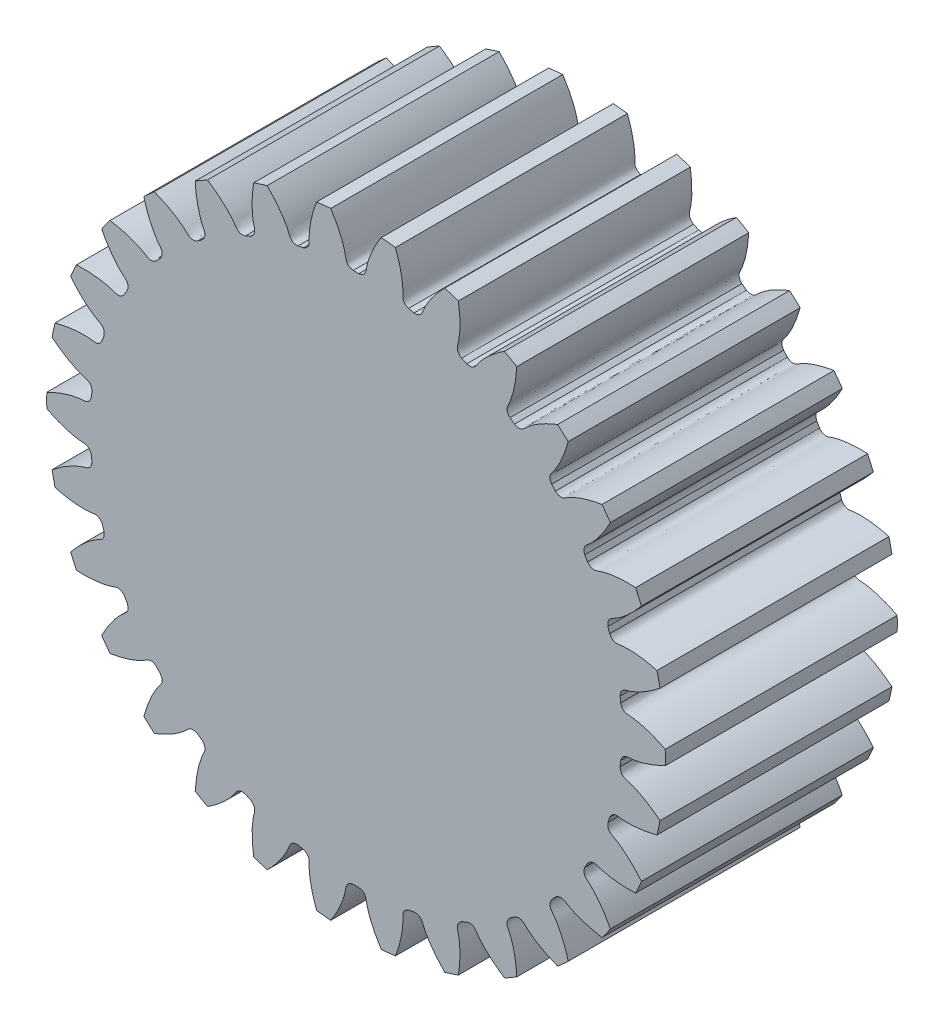
SolidWorks part; units mm, degrees
ref_plane "前视基准面" through (0, 0, 0) normal (0, 0, 1) x (1, 0, 0)
ref_plane "上视基准面" through (0, 0, 0) normal (0, 1, 0) x (1, 0, 0)
ref_plane "右视基准面" through (0, 0, 0) normal (1, 0, 0) x (0, 0, -1)
sketch "草图1" plane through (0, 0, 0) normal (0, 0, 1) x (1, 0, 0)
  circle A0 centre (0, 0) radius 40
extrude "凸台-拉伸1" add sketch "草图1" along normal blind 30
ref_axis "基准轴1" through (0, 0, 30) along (0, 0, -1)
sketch "草图2" plane through (0, 0, 0) normal (0, 0, 1) x (1, 0, 0)
  line L0 (0, 0) -> (0, 40) construction
  circle A0 centre (0, 0) radius 40 construction
  arc A1 (0.3639, 34.3731) -> (-0.3639, 34.3731) centre (0, 0) ccw
  arc A2 (8.4158, 45.4764) -> (-8.4158, 45.4764) centre (0, 0) ccw
  spline S0 degree 3 poles (0.3639, 34.3731) (1.2706, 34.5324) (1.2758, 35.1178) (1.3975, 35.7214) (1.4249, 35.8453) (1.4581, 35.9823) (1.4977, 36.1322) (1.5441, 36.2949) (1.5979, 36.4701) (1.6595, 36.6576) (1.7296, 36.8571) (1.8086, 37.0683) (1.897, 37.2911) (1.9953, 37.525) (2.1039, 37.7698) (2.2234, 38.0251) (2.3543, 38.2907) (2.4968, 38.5661) (2.6516, 38.851) (2.819, 39.1449) (2.9995, 39.4476) (3.1935, 39.7586) (3.4013, 40.0774) (3.6234, 40.4037) (3.8602, 40.737) (4.1119, 41.0768) (4.379, 41.4226) (4.6618, 41.774) (4.9607, 42.1305) (5.2758, 42.4916) (5.6076, 42.8567) (5.9564, 43.2254) (6.3223, 43.597) (6.7057, 43.9711) (7.1067, 44.3471) (7.6723, 44.8566) (8.1134, 45.2302) (8.4158, 45.4764) knots 0 0 0 0 0.115324 0.123413 0.132512 0.142623 0.153745 0.165878 0.179022 0.193177 0.208343 0.22452 0.241708 0.259907 0.279117 0.299338 0.320571 0.342814 0.366068 0.390334 0.41561 0.441898 0.469196 0.497506 0.526827 0.557158 0.588501 0.620855 0.65422 0.688595 0.723982 0.76038 0.797789 0.836209 0.87564 0.916083 1 1 1 1
  spline S1 degree 3 poles (-0.3639, 34.3731) (-1.2706, 34.5324) (-1.2758, 35.1178) (-1.3975, 35.7214) (-1.4249, 35.8453) (-1.4581, 35.9823) (-1.4977, 36.1322) (-1.5441, 36.2949) (-1.5979, 36.4701) (-1.6595, 36.6576) (-1.7296, 36.8571) (-1.8086, 37.0683) (-1.897, 37.2911) (-1.9953, 37.525) (-2.1039, 37.7698) (-2.2234, 38.0251) (-2.3543, 38.2907) (-2.4968, 38.5661) (-2.6516, 38.851) (-2.819, 39.1449) (-2.9995, 39.4476) (-3.1935, 39.7586) (-3.4013, 40.0774) (-3.6234, 40.4037) (-3.8602, 40.737) (-4.1119, 41.0768) (-4.379, 41.4226) (-4.6618, 41.774) (-4.9607, 42.1305) (-5.2758, 42.4916) (-5.6076, 42.8567) (-5.9564, 43.2254) (-6.3223, 43.597) (-6.7057, 43.9711) (-7.1067, 44.3471) (-7.6723, 44.8566) (-8.1134, 45.2302) (-8.4158, 45.4764) knots 0 0 0 0 0.115324 0.123413 0.132512 0.142623 0.153745 0.165878 0.179022 0.193177 0.208343 0.22452 0.241708 0.259907 0.279117 0.299338 0.320571 0.342814 0.366068 0.390334 0.41561 0.441898 0.469196 0.497506 0.526827 0.557158 0.588501 0.620855 0.65422 0.688595 0.723982 0.76038 0.797789 0.836209 0.87564 0.916083 1 1 1 1
extrude "切除-拉伸1" cut sketch "草图2" along normal through all
pattern_circular "阵列(圆周)1" count 30 every 12 about axis through (0, 0, 30) along (0, 0, -1) of "切除-拉伸1"
sketch "草图3" plane through (0, 0, 0) normal (0, 0, 1) x (1, 0, 0)
  circle A0 centre (0, 0) radius 37.5 construction
  dimension "Dn" = 75
sketch "草图4" plane through (0, 0, 30) normal (0, 0, 1) x (1, 0, 0)
  point P0 (0, 0)
sketch "草图5" plane through (0, 0, 30) normal (0, 0, 1) x (1, 0, 0)
  line L0 (0, 0) -> (0, 14.1703)
  point P4 (0, 0)
